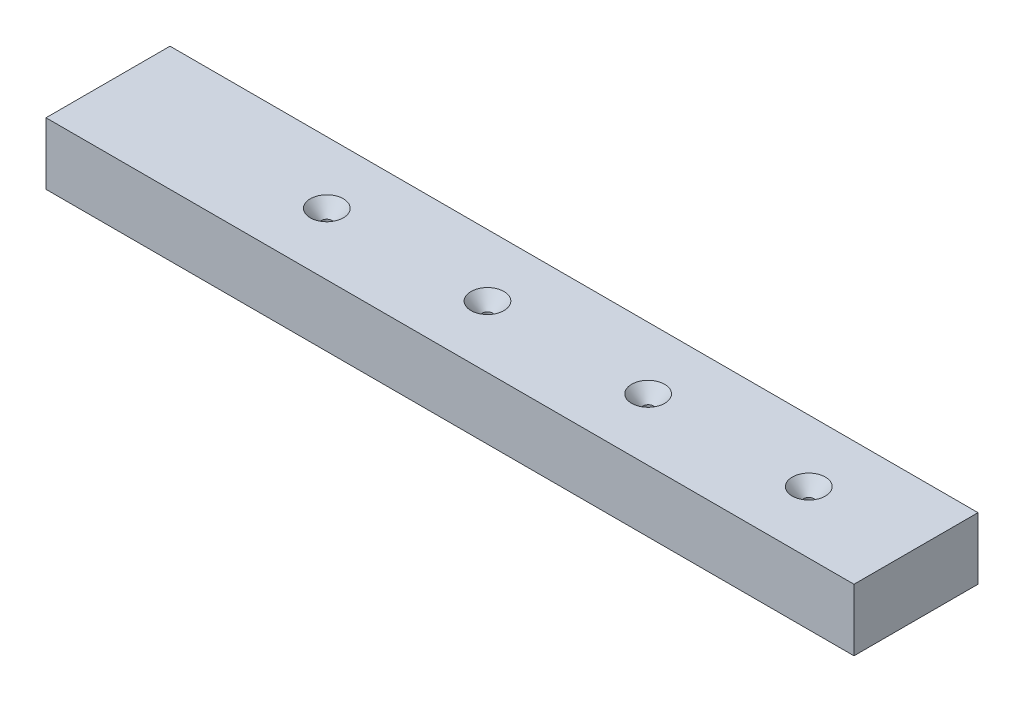
SolidWorks part; units mm, degrees
material "Beech"
ref_plane "Front Plane" through (0, 0, 0) normal (0, 0, 1) x (1, 0, 0)
ref_plane "Top Plane" through (0, 0, 0) normal (0, 1, 0) x (1, 0, 0)
ref_plane "Right Plane" through (0, 0, 0) normal (1, 0, 0) x (0, 0, -1)
sketch "Sketch1" plane through (0, 0, 0) normal (0, 0, 1) x (1, 0, 0)
  line L0 (248.25, 82.8417) -> (248.25, -188.5238) construction
  line L1 (248.25, 38.1) -> (0, 38.1)
  line L2 (248.25, 38.1) -> (248.25, 57.15)
  line L3 (248.25, 57.15) -> (0, 57.15)
  line L4 (0, 38.1) -> (0, 57.15)
  line L5 (-12.7, 38.1) -> (267.3, 38.1) construction
  line L6 (0, 82.8417) -> (0, -188.5238) construction
  dimension "D1" = 19.05
extrude "Boss-Extrude1" add sketch "Sketch1" along normal blind 38.1
hole_wizard "Hole1" positions "Sketch2" profile "Sketch3" legacy
sketch "Sketch2" plane through (-1073.3642, -52.975, -12.7) normal (0, 0, -1) x (0, 1, 0)
  line L0 (100.6, 1338.7628) -> (100.6, 1090.5128) construction
  line L6 (0.134, 1338.7628) -> (0.134, 1090.5128) construction
  point P12 (100.6, 1313.3628)
  point P14 (100.6, 1115.9128)
  point P16 (100.6, 1214.6378)
  point P22 (-100.332, 1214.6378)
  point P23 (-100.332, 1115.9128)
  point P24 (-100.332, 1313.3628)
sketch "Sketch3" plane through (239.9986, -153.307, -12.7) normal (1, 0, 0) x (0, 1, 0)
  line L0 (0, 0) -> (0, 32.7039)
  line L1 (0, 32.7039) -> (1.5875, 31.75)
  line L2 (1.5875, 31.75) -> (1.5875, 4.0177)
  line L3 (1.5875, 4.0177) -> (5.08, 0)
  line L4 (5.08, 0) -> (0, 0)
  line L5 (0, -14.3089) -> (0, 102.4216) construction
  line L6 (0, 32.7039) -> (-1.5875, 31.75) construction
  line L7 (-1.5875, 4.0177) -> (-5.08, 0) construction
  dimension "Diameter" = 3.175
  dimension "Depth" = 31.75
  dimension "C-Sink Diameter" = 10.16
  dimension "C-Sink Angle" = 82
  dimension "Drill Angle" = 118
hole_wizard "Hole2" positions "Sketch4" profile "Sketch5" legacy
sketch "Sketch4" plane through (-1073.3642, 57.15, -415.7924) normal (0, 1, 0) x (0.3746, 0, 0.9272)
  line L0 (904.6882, 1078.3844) -> (811.6921, 848.211) construction
  line L4 (858.1902, 963.2977) -> (876.6817, 1009.0658)
  line L5 (876.6817, 1009.0658) -> (895.1732, 1054.8339)
  line L7 (858.1902, 963.2977) -> (875.853, 956.1614) construction
  point P20 (885.9274, 1031.9499)
  point P22 (867.4359, 986.1818)
  point P25 (830.4529, 894.6455)
  point P26 (848.9444, 940.4136)
sketch "Sketch5" plane through (116.5923, 57.15, 19.05) normal (1, 0, 0) x (0, 0, 1)
  line L0 (0, 0) -> (0, 58.1039)
  line L1 (0, 58.1039) -> (1.5875, 57.15)
  line L2 (1.5875, 57.15) -> (1.5875, 4.0177)
  line L3 (1.5875, 4.0177) -> (5.08, 0)
  line L4 (5.08, 0) -> (0, 0)
  line L5 (0, -14.3089) -> (0, 102.4216) construction
  line L6 (0, 58.1039) -> (-1.5875, 57.15) construction
  line L7 (-1.5875, 4.0177) -> (-5.08, 0) construction
  dimension "Diameter" = 3.175
  dimension "Depth" = 57.15
  dimension "C-Sink Diameter" = 10.16
  dimension "C-Sink Angle" = 82
  dimension "Drill Angle" = 118
